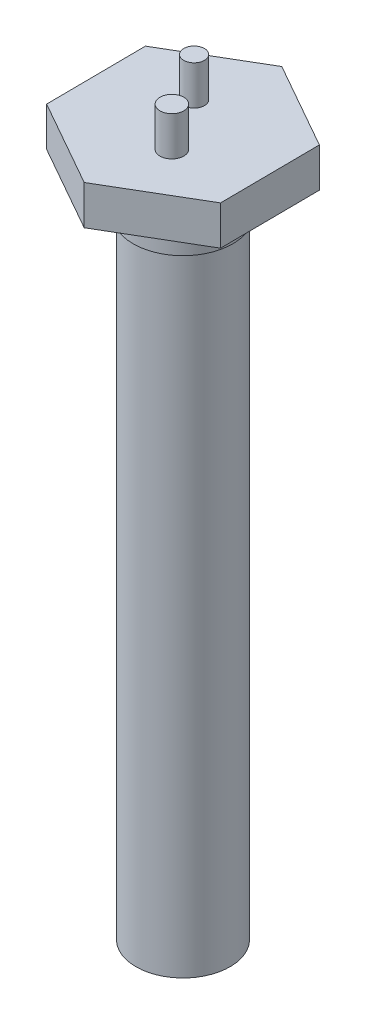
SolidWorks part; units mm, degrees
note: The reader was unsure of these and kept them because the rebuilt part matched: shared geometry of "Sketch1<12>", "Sketch1<15>", "Sketch1<17>", "Sketch1<19>", "Sketch1<20>".
ref_plane "Front Plane" through (0, 0, 0) normal (0, 0, 1) x (1, 0, 0)
ref_plane "Top Plane" through (0, 0, 0) normal (0, 1, 0) x (1, 0, 0)
ref_plane "Right Plane" through (0, 0, 0) normal (1, 0, 0) x (0, 0, -1)
sketch "Sketch1" plane through (0, 0, 0) normal (0, 1, 0) x (1, 0, 0)
  line L0 (-12.6451, 45.9365) -> (-8.5882, 39.0414)
  line L1 (13.5126, 26.5228) -> (13.3036, 51.922)
  line L2 (13.3036, 51.922) -> (-8.7972, 64.4406)
  line L3 (-8.7972, 64.4406) -> (-30.689, 51.56)
  line L4 (-30.689, 51.56) -> (-30.48, 26.1609)
  line L5 (-30.48, 26.1609) -> (-8.3793, 13.6423)
  line L6 (-8.3793, 13.6423) -> (13.5126, 26.5228)
  line L7 (-8.5882, 39.0414) -> (-4.5314, 32.1464)
  circle A0 centre (-8.5882, 39.0414) radius 21.997 construction
  circle A1 centre (-12.6451, 45.9365) radius 2.6302
  circle A2 centre (-4.5314, 32.1464) radius 3.0267
  circle A3 centre (-8.5882, 39.0414) radius 12.7
  circle A4 centre (-8.5882, 39.0414) radius 12
  dimension "D2" = 25.4
  dimension "D3" = 24
  dimension "D1" = 25.4
  dimension "D4" = 8
  dimension "D5" = 8
extrude "Boss-Extrude4" add sketch "Sketch1" along normal blind 180
extrude "Boss-Extrude7" add sketch "Sketch1<12>" along normal blind 170
sketch "Sketch1<12>" plane through (0, 0, 0) normal (0, 1, 0) x (1, 0, 0) same geometry as "Sketch1"
extrude "Cut-Extrude1" cut sketch "Sketch1<15>" along normal blind 170
sketch "Sketch1<15>" plane through (0, 0, 0) normal (0, 1, 0) x (1, 0, 0) same geometry as "Sketch1"
extrude "Boss-Extrude8" add sketch "Sketch1<17>" along normal blind 170
sketch "Sketch1<17>" plane through (0, 0, 0) normal (0, 1, 0) x (1, 0, 0) same geometry as "Sketch1"
extrude "Cut-Extrude4" cut sketch "Sketch1<19>" along normal blind 160 contours A3 A4
sketch "Sketch1<19>" plane through (0, 0, 0) normal (0, 1, 0) x (1, 0, 0) same geometry as "Sketch1"
extrude "Boss-Extrude9" add sketch "Sketch1<20>" along normal blind 190
sketch "Sketch1<20>" plane through (0, 0, 0) normal (0, 1, 0) x (1, 0, 0) same geometry as "Sketch1"
